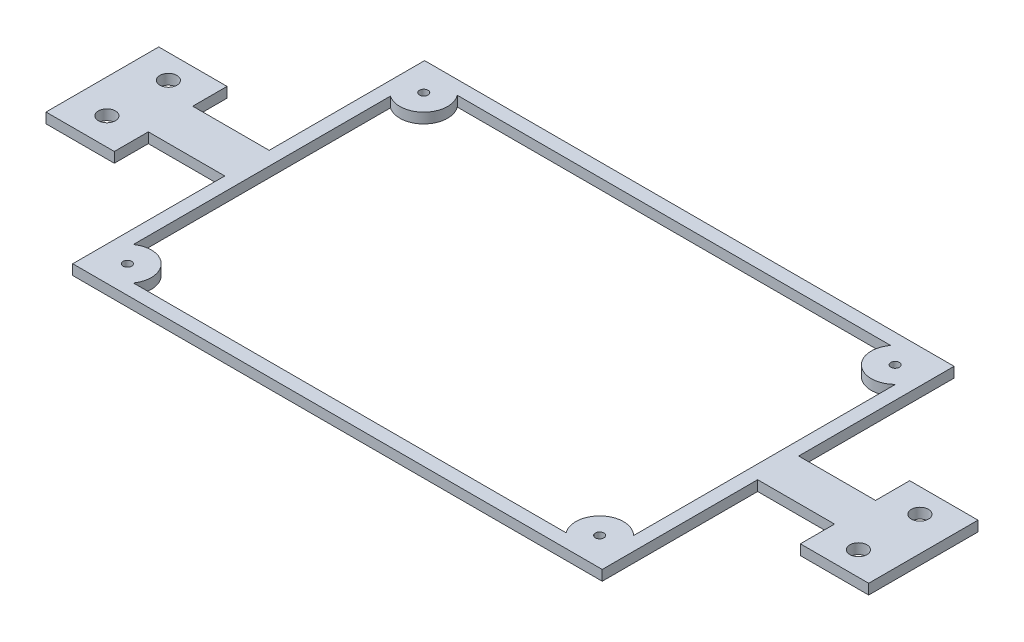
SolidWorks part; units mm, degrees
ref_plane "Front Plane" through (0, 0, 0) normal (0, 0, 1) x (1, 0, 0)
ref_plane "Top Plane" through (0, 0, 0) normal (0, 1, 0) x (1, 0, 0)
ref_plane "Right Plane" through (0, 0, 0) normal (1, 0, 0) x (0, 0, -1)
sketch "Sketch1" plane through (0, 0, 0) normal (0, 1, 0) x (1, 0, 0)
  line L1 (0, 0) -> (155, 0)
  line L2 (0, 0) -> (0, 103)
  line L3 (0, 103) -> (155, 103)
  line L4 (155, 0) -> (155, 103)
  line L5 (4, 4) -> (151, 4)
  line L6 (4, 4) -> (4, 99)
  line L7 (4, 99) -> (151, 99)
  line L8 (151, 4) -> (151, 99)
extrude "Boss-Extrude2" add sketch "Sketch1" along normal blind 3
sketch "Sketch2" plane through (0, 3, 0) normal (0, 1, 0) x (1, 0, 0)
  circle A0 centre (8, 8) radius 1.25
  circle A1 centre (8, 8) radius 7
  circle A2 centre (146, 8.25) radius 1.25
  circle A3 centre (146, 8.25) radius 7
  circle A4 centre (8, 94.75) radius 7
  circle A5 centre (8, 94.75) radius 1.25
  circle A6 centre (146, 94.75) radius 7
  circle A7 centre (146, 94.75) radius 1.25
sketch "Sketch3" plane through (0, 0, 0) normal (-1, 0, 0) x (0, 0, 1)
  line L1 (-57.5, 0) -> (-44.5, 0)
  line L2 (-57.5, 0) -> (-57.5, 3)
  line L3 (-57.5, 3) -> (-44.5, 3)
  line L4 (-44.5, 0) -> (-44.5, 3)
extrude "Boss-Extrude5" add sketch "Sketch3" along normal blind 22.5
sketch "Sketch4" plane through (155, 0, 0) normal (1, 0, 0) x (0, 0, -1)
  line L1 (57.5, 3) -> (45.5, 3)
  line L2 (57.5, 3) -> (57.5, 0)
  line L3 (57.5, 0) -> (45.5, 0)
  line L4 (45.5, 3) -> (45.5, 0)
extrude "Boss-Extrude6" add sketch "Sketch4" along normal blind 22.5
sketch "Sketch5" plane through (0, 3, 0) normal (0, 1, 0) x (1, 0, 0)
  line L1 (177.5, 67.5) -> (197.5, 67.5)
  line L2 (177.5, 67.5) -> (177.5, 35.5)
  line L3 (177.5, 35.5) -> (197.5, 35.5)
  line L4 (197.5, 67.5) -> (197.5, 35.5)
  circle A0 centre (187.5, 60.5) radius 2.5
  circle A1 centre (187.5, 42.5) radius 2.5
extrude "Boss-Extrude7" add sketch "Sketch5" against normal blind 3
sketch "Sketch6" plane through (0, 3, 0) normal (0, 1, 0) x (1, 0, 0)
  line L1 (-22.3784, 67.5504) -> (-42.3784, 67.5504)
  line L2 (-22.3784, 67.5504) -> (-22.3784, 34.5504)
  line L3 (-22.3784, 34.5504) -> (-42.3784, 34.5504)
  line L4 (-42.3784, 67.5504) -> (-42.3784, 34.5504)
  circle A0 centre (-32.5, 60.5) radius 2.5
  circle A1 centre (-32.5, 42.5) radius 2.5
extrude "Boss-Extrude8" add sketch "Sketch6" against normal blind 3
extrude "Boss-Extrude11" add sketch "Sketch2<3>" against normal blind 3
sketch "Sketch2<3>" plane through (0, 3, 0) normal (0, 1, 0) x (1, 0, 0) same geometry as "Sketch2"
extrude "Boss-Extrude10" add sketch "Sketch2" against normal blind 3
